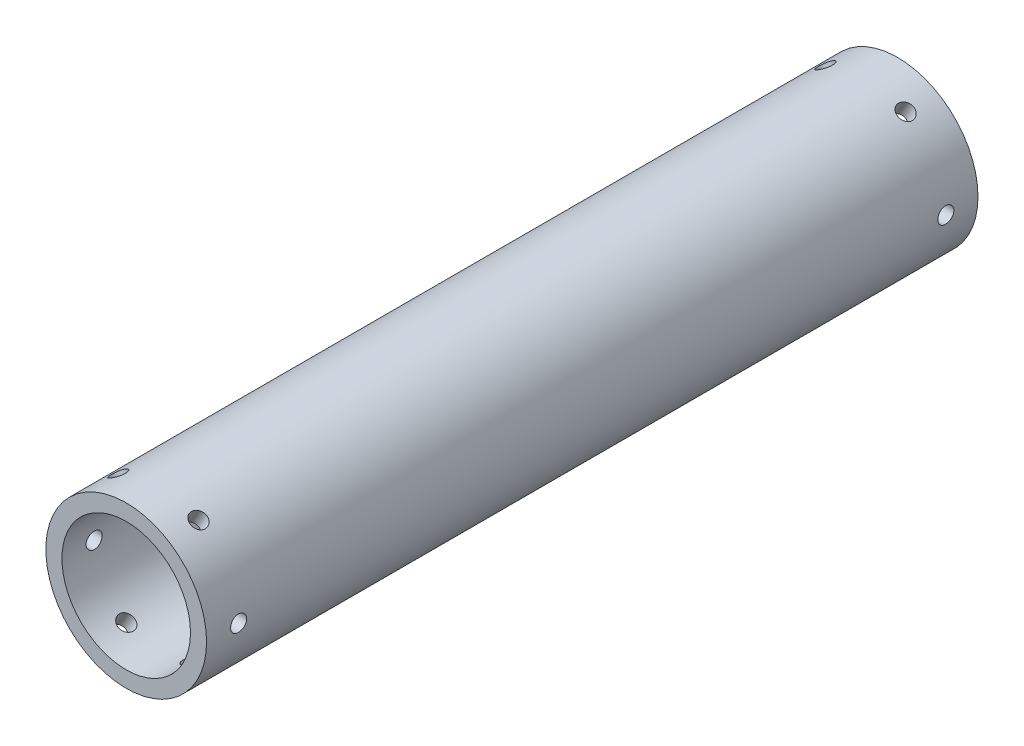
SolidWorks part; units mm, degrees
ref_plane "Front Plane" through (0, 0, 0) normal (1, 0, 0) x (0, 1, 0)
ref_plane "Top Plane" through (0, 0, 0) normal (0, 0, 1) x (0, 1, 0)
ref_plane "Right Plane" through (0, 0, 0) normal (0, 1, 0) x (-1, 0, 0)
sketch "Sketch2" plane through (0, 0, 0) normal (0, 0, 1) x (0, 1, 0)
  line L0 (0, 0) -> (31.75, 0) construction
  circle A0 centre (0, 0) radius 31.75
  circle A1 centre (0, 0) radius 25.4
  dimension "D1" = 50.8
  dimension "D2" = 6.35
extrude "base" add sketch "Sketch2" along normal blind 304.8
ref_plane "Plane1" through (-31.75, 0, 0) normal (-1, 0, 0) x (0, 0, 1)
sketch "Sketch3" plane through (-31.75, 0, 0) normal (-1, 0, 0) x (0, 0, 1)
  line L0 (0, 0) -> (304.8, 0) construction
  line L1 (0, -31.75) -> (0, 31.75) construction
  line L2 (304.8, -31.75) -> (304.8, 31.75) construction
  line L3 (0, 0) -> (0, 31.75) construction
  circle A0 centre (12.7, 0) radius 3.175
  circle A1 centre (292.1, 0) radius 3.175
  dimension "D1" = 6.35
  dimension "D3" = 6.35
  dimension "D2" = 12.7
  dimension "D4" = 12.7
extrude "boltholes" cut sketch "Sketch3" against normal up to next
pattern_circular "CirPattern1" count 6 over 360 about axis through (0, 0, 304.8) along (0, 0, -1) of "boltholes" reverse direction yes
